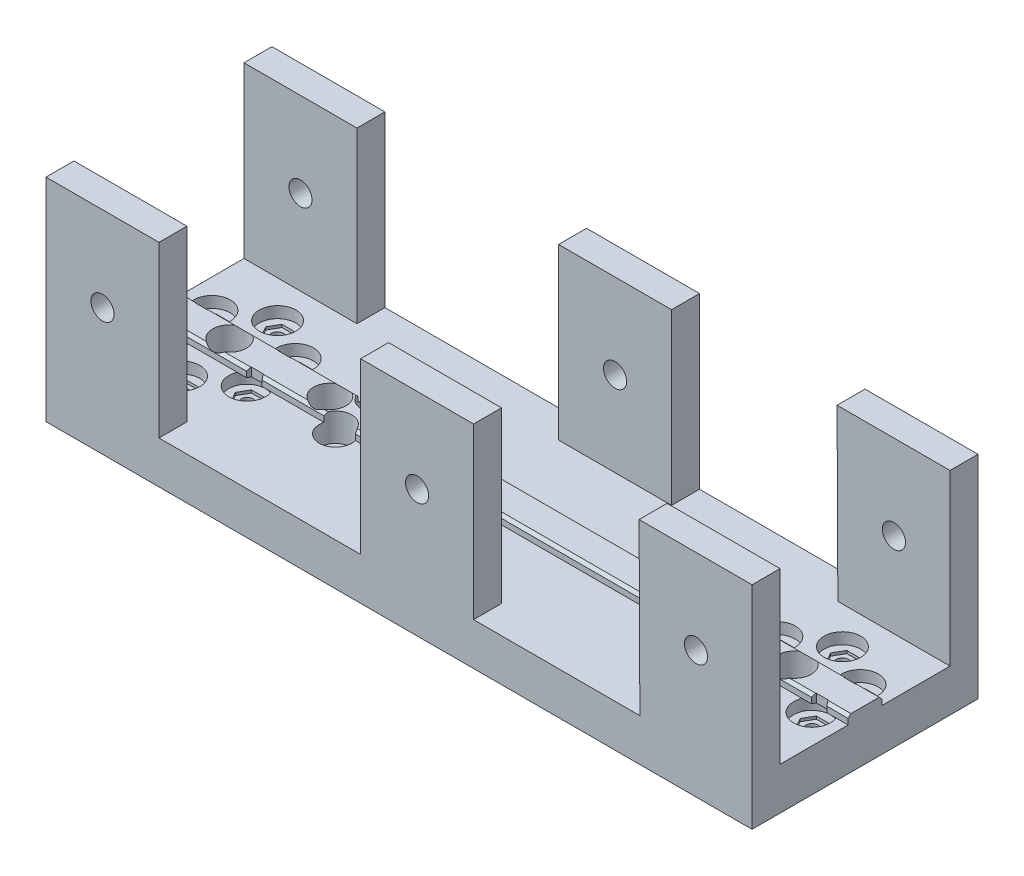
SolidWorks part; units mm, degrees
ref_plane "Płaszczyzna przednia" through (0, 0, 0) normal (0, 0, 1) x (1, 0, 0)
ref_plane "Płaszczyzna górna" through (0, 0, 0) normal (0, 1, 0) x (1, 0, 0)
ref_plane "Płaszczyzna prawa" through (0, 0, 0) normal (1, 0, 0) x (0, 0, -1)
sketch "Sketch1" plane through (0, 0, 0) normal (0, 1, 0) x (1, 0, 0)
  line L0 (250, 60) -> (250, 0)
  line L1 (0, 0) -> (250, 0)
  line L2 (0, 0) -> (0, 60)
  line L3 (0, 60) -> (250, 60)
  line L5 (125, 0) -> (125, 102.1995) construction
  circle A0 centre (25, 30) radius 17 construction
  circle A2 centre (25, 13) radius 2.2
  circle A3 centre (10.2776, 21.5) radius 2.2
  circle A4 centre (10.2776, 38.5) radius 2.2
  circle A5 centre (25, 47) radius 2.2
  circle A6 centre (39.7224, 38.5) radius 2.2
  circle A7 centre (39.7224, 21.5) radius 2.2
  circle A8 centre (225, 30) radius 17 construction
  circle A9 centre (210.2776, 21.5) radius 2.2
  circle A10 centre (210.2776, 38.5) radius 2.2
  circle A11 centre (225, 47) radius 2.2
  circle A12 centre (239.7224, 38.5) radius 2.2
  circle A13 centre (239.7224, 21.5) radius 2.2
  circle A14 centre (225, 13) radius 2.2
  point P24 (25, 30)
  point P36 (225, 30)
  dimension "D7" = 34
  dimension "D9" = 4.4
  dimension "D1" = 250
  dimension "D2" = 60
  dimension "D3" = 30
  dimension "D4" = 25
  dimension "D10" = 6
extrude "Boss-Extrude1" add sketch "Sketch1" along normal blind 15
sketch "Sketch2" plane through (0, 0, 0) normal (0, 1, 0) x (1, 0, 0)
  line L0 (250, 0) -> (250, 60) construction
  line L1 (0, 36) -> (250, 36)
  line L2 (0, 36) -> (0, 24)
  line L3 (0, 24) -> (250, 24)
  line L4 (250, 36) -> (250, 24)
  line L5 (0, 60) -> (0, 0) construction
  line L6 (0, 0) -> (250, 0) construction
  line L7 (250, 60) -> (0, 60) construction
  dimension "D1" = 24
  dimension "D2" = 24
extrude "Boss-Extrude2" add sketch "Sketch2" along normal blind 3 from surface starting at face at (125, 15, -30)
chamfer "Chamfer1" distance 1 angle 45 2 edges at (125, 18, -36) (125, 18, -24)
sketch "Sketch3" plane through (0, 0, 0) normal (0, 1, 0) x (1, 0, 0)
  line L0 (125, 0) -> (125, 70.4894) construction
  line L1 (29.2, 13) -> (27.1, 16.6373)
  line L2 (27.1, 16.6373) -> (22.9, 16.6373)
  line L3 (22.9, 16.6373) -> (20.8, 13)
  line L4 (20.8, 13) -> (22.9, 9.3627)
  line L5 (22.9, 9.3627) -> (27.1, 9.3627)
  line L6 (27.1, 9.3627) -> (29.2, 13)
  line L7 (29.2, 47) -> (27.1, 50.6373)
  line L8 (27.1, 50.6373) -> (22.9, 50.6373)
  line L9 (22.9, 50.6373) -> (20.8, 47)
  line L10 (20.8, 47) -> (22.9, 43.3627)
  line L11 (22.9, 43.3627) -> (27.1, 43.3627)
  line L12 (27.1, 43.3627) -> (29.2, 47)
  line L13 (43.9224, 38.5) -> (41.8224, 42.1373)
  line L14 (41.8224, 42.1373) -> (37.6224, 42.1373)
  line L15 (37.6224, 42.1373) -> (35.5224, 38.5)
  line L16 (35.5224, 38.5) -> (37.6224, 34.8627)
  line L17 (37.6224, 34.8627) -> (41.8224, 34.8627)
  line L18 (41.8224, 34.8627) -> (43.9224, 38.5)
  line L19 (43.9224, 21.5) -> (41.8224, 25.1373)
  line L20 (41.8224, 25.1373) -> (37.6224, 25.1373)
  line L21 (37.6224, 25.1373) -> (35.5224, 21.5)
  line L22 (35.5224, 21.5) -> (37.6224, 17.8627)
  line L23 (37.6224, 17.8627) -> (41.8224, 17.8627)
  line L24 (41.8224, 17.8627) -> (43.9224, 21.5)
  line L25 (14.4776, 21.5) -> (12.3776, 25.1373)
  line L26 (12.3776, 25.1373) -> (8.1776, 25.1373)
  line L27 (8.1776, 25.1373) -> (6.0776, 21.5)
  line L28 (6.0776, 21.5) -> (8.1776, 17.8627)
  line L29 (8.1776, 17.8627) -> (12.3776, 17.8627)
  line L30 (12.3776, 17.8627) -> (14.4776, 21.5)
  line L31 (14.4776, 38.5) -> (12.3776, 42.1373)
  line L32 (12.3776, 42.1373) -> (8.1776, 42.1373)
  line L33 (8.1776, 42.1373) -> (6.0776, 38.5)
  line L34 (6.0776, 38.5) -> (8.1776, 34.8627)
  line L35 (8.1776, 34.8627) -> (12.3776, 34.8627)
  line L36 (12.3776, 34.8627) -> (14.4776, 38.5)
  line L37 (0, 0) -> (250, 0) construction
  line L38 (237.6224, 34.8627) -> (235.5224, 38.5)
  line L39 (241.8224, 34.8627) -> (237.6224, 34.8627)
  line L40 (243.9224, 38.5) -> (241.8224, 34.8627)
  line L41 (241.8224, 42.1373) -> (243.9224, 38.5)
  line L42 (237.6224, 42.1373) -> (241.8224, 42.1373)
  line L43 (235.5224, 38.5) -> (237.6224, 42.1373)
  line L44 (237.6224, 17.8627) -> (235.5224, 21.5)
  line L45 (241.8224, 17.8627) -> (237.6224, 17.8627)
  line L46 (243.9224, 21.5) -> (241.8224, 17.8627)
  line L47 (241.8224, 25.1373) -> (243.9224, 21.5)
  line L48 (237.6224, 25.1373) -> (241.8224, 25.1373)
  line L49 (235.5224, 21.5) -> (237.6224, 25.1373)
  line L50 (208.1776, 17.8627) -> (206.0776, 21.5)
  line L51 (212.3776, 17.8627) -> (208.1776, 17.8627)
  line L52 (214.4776, 21.5) -> (212.3776, 17.8627)
  line L53 (212.3776, 25.1373) -> (214.4776, 21.5)
  line L54 (208.1776, 25.1373) -> (212.3776, 25.1373)
  line L55 (206.0776, 21.5) -> (208.1776, 25.1373)
  line L56 (208.1776, 34.8627) -> (206.0776, 38.5)
  line L57 (212.3776, 34.8627) -> (208.1776, 34.8627)
  line L58 (214.4776, 38.5) -> (212.3776, 34.8627)
  line L59 (212.3776, 42.1373) -> (214.4776, 38.5)
  line L60 (208.1776, 42.1373) -> (212.3776, 42.1373)
  line L61 (206.0776, 38.5) -> (208.1776, 42.1373)
  line L62 (222.9, 43.3627) -> (220.8, 47)
  line L63 (227.1, 43.3627) -> (222.9, 43.3627)
  line L64 (229.2, 47) -> (227.1, 43.3627)
  line L65 (227.1, 50.6373) -> (229.2, 47)
  line L66 (222.9, 50.6373) -> (227.1, 50.6373)
  line L67 (220.8, 47) -> (222.9, 50.6373)
  line L68 (222.9, 9.3627) -> (220.8, 13)
  line L69 (227.1, 9.3627) -> (222.9, 9.3627)
  line L70 (229.2, 13) -> (227.1, 9.3627)
  line L71 (227.1, 16.6373) -> (229.2, 13)
  line L72 (222.9, 16.6373) -> (227.1, 16.6373)
  line L73 (220.8, 13) -> (222.9, 16.6373)
  circle A0 centre (25, 13) radius 3.6373 construction
  circle A1 centre (25, 47) radius 3.6373 construction
  circle A2 centre (39.7224, 38.5) radius 3.6373 construction
  circle A3 centre (39.7224, 21.5) radius 3.6373 construction
  circle A4 centre (10.2776, 21.5) radius 3.6373 construction
  circle A5 centre (10.2776, 38.5) radius 3.6373 construction
  circle A6 centre (239.7224, 38.5) radius 3.6373 construction
  circle A7 centre (239.7224, 21.5) radius 3.6373 construction
  circle A8 centre (210.2776, 21.5) radius 3.6373 construction
  circle A9 centre (210.2776, 38.5) radius 3.6373 construction
  circle A10 centre (225, 47) radius 3.6373 construction
  circle A11 centre (225, 13) radius 3.6373 construction
  dimension "D1" = 8.4
  dimension "D2" = 8.4
  dimension "D3" = 8.4
  dimension "D4" = 8.4
  dimension "D5" = 8.4
  dimension "D6" = 8.4
extrude "Cut-Extrude1" cut sketch "Sketch3" against normal blind 8 from surface starting at face at (125, 18, -30)
sketch "Sketch4" plane through (0, 0, 0) normal (0, 1, 0) x (1, 0, 0)
  line L0 (125, 0) -> (125, 76.4664) construction
  line L1 (0, 0) -> (250, 0) construction
  circle A0 centre (25, 13) radius 6.5
  circle A1 centre (10.2776, 21.5) radius 6.5
  circle A2 centre (39.7224, 21.5) radius 6.5
  circle A3 centre (39.7224, 38.5) radius 6.5
  circle A4 centre (25, 47) radius 6.5
  circle A5 centre (10.2776, 38.5) radius 6.5
  circle A6 centre (239.7224, 38.5) radius 6.5
  circle A7 centre (225, 47) radius 6.5
  circle A8 centre (210.2776, 38.5) radius 6.5
  circle A9 centre (210.2776, 21.5) radius 6.5
  circle A10 centre (239.7224, 21.5) radius 6.5
  circle A11 centre (225, 13) radius 6.5
  dimension "D1" = 13
extrude "Cut-Extrude2" cut sketch "Sketch4" against normal blind 4 from surface starting at face at (25, 15, -13)
sketch "Sketch5" plane through (0, 0, 0) normal (0, 1, 0) x (1, 0, 0)
  line L0 (60.5, 30) -> (79.5, 30) construction
  line L1 (70, 30) -> (70, 22.5) construction
  line L2 (70, 30) -> (70, 37.5) construction
  line L3 (0, 0) -> (250, 0) construction
  line L4 (0, 60) -> (0, 0) construction
  circle A0 centre (60.5, 30) radius 3
  circle A1 centre (70, 22.5) radius 3
  circle A2 centre (70, 37.5) radius 3
  circle A3 centre (79.5, 30) radius 3
  dimension "D4" = 6
  dimension "D5" = 30
  dimension "D1" = 19
  dimension "D2" = 15
  dimension "D3" = 7.5
  dimension "D6" = 70
extrude "Cut-Extrude3" cut sketch "Sketch5" along normal through all both and the other way through all
sketch "Sketch6" plane through (0, 0, 0) normal (0, 1, 0) x (1, 0, 0)
  circle A0 centre (60.5, 30) radius 5.75
  circle A1 centre (70, 37.5) radius 5.75
  circle A2 centre (79.5, 30) radius 5.75
  circle A3 centre (70, 22.5) radius 5.75
  dimension "D1" = 11.5
extrude "Cut-Extrude7" cut sketch "Sketch6" against normal blind 10 from surface starting at face at (60.5, 18, -27)
sketch "Sketch7" plane through (0, 0, 0) normal (0, 1, 0) x (1, 0, 0)
  line L0 (250, 60) -> (0, 60) construction
  line L1 (250, 0) -> (250, 24) construction
  line L2 (0, 35) -> (0, 25) construction
  line L3 (0, 0) -> (250, 0) construction
  circle A0 centre (225, 30) radius 5.95
  circle A1 centre (25, 30) radius 5.95
  dimension "D3" = 11.9
  dimension "D4" = 11.9
  dimension "D1" = 30
  dimension "D2" = 25
  dimension "D5" = 25
  dimension "D6" = 30
extrude "Cut-Extrude13" cut sketch "Sketch7" along normal through all both
sketch "Sketch9" plane through (0, 0, 0) normal (0, 0, 1) x (1, 0, 0)
  line L1 (0, 0) -> (250, 0)
  line L2 (0, 0) -> (0, 75)
  line L3 (0, 75) -> (40, 75)
  line L7 (111.3949, 75) -> (151.3949, 75)
  line L9 (0, 15) -> (250, 15) construction
  line L11 (250, 0) -> (250, 75)
  line L12 (250, 75) -> (210, 75)
  line L14 (75.5509, 15) -> (204.2776, 15) construction
  line L15 (216.2776, 15) -> (233.7224, 15) construction
  line L16 (0, 45) -> (250, 45) construction
  line L17 (40, 75) -> (40, 15)
  line L18 (40, 15) -> (111.3949, 15)
  line L19 (111.3949, 15) -> (111.3949, 75)
  line L20 (0, 0) -> (250, 0) construction
  line L21 (151.3949, 75) -> (151.3949, 15)
  line L22 (151.3949, 15) -> (210.2776, 15)
  line L23 (208.1776, 15) -> (212.3776, 15) construction
  line L24 (210.2776, 15) -> (210, 75)
  circle A0 centre (20, 45) radius 4.1
  circle A1 centre (131.3949, 45) radius 4.1
  circle A2 centre (230.139, 45) radius 4.1
  point P30 (111.3949, 76.1129)
  dimension "D8" = 8.2
  dimension "D1" = 60
  dimension "D2" = 60
  dimension "D3" = 60
  dimension "D4" = 40
  dimension "D5" = 40
  dimension "D6" = 40
  dimension "D7" = 30
  dimension "D9" = 20
  dimension "D10" = 20
  dimension "D11" = 20
extrude "Boss-Extrude3" add sketch "Sketch9" along normal blind 10
extrude "Boss-Extrude4" add sketch "Sketch9<3>" against normal blind 10 from surface starting at face at (125, 7.5, -60)
sketch "Sketch9<3>" plane through (0, 0, 0) normal (0, 0, 1) x (1, 0, 0) same geometry as "Sketch9"
sketch "Sketch11" plane through (0, 0, 0) normal (0, 0, 1) x (1, 0, 0)
  line L1 (0, 75) -> (250, 75)
  line L2 (0, 75) -> (0, 15)
  line L3 (0, 15) -> (250, 15)
  line L4 (250, 75) -> (250, 15)
extrude "Cut-Extrude14" cut sketch "Sketch11" along normal blind 0.1
extrude "Cut-Extrude15" cut sketch "Sketch11<2>" against normal blind 0.1 from surface starting at face at (234.239, 45, -60)
sketch "Sketch11<2>" plane through (0, 0, 0) normal (0, 0, 1) x (1, 0, 0) same geometry as "Sketch11"
